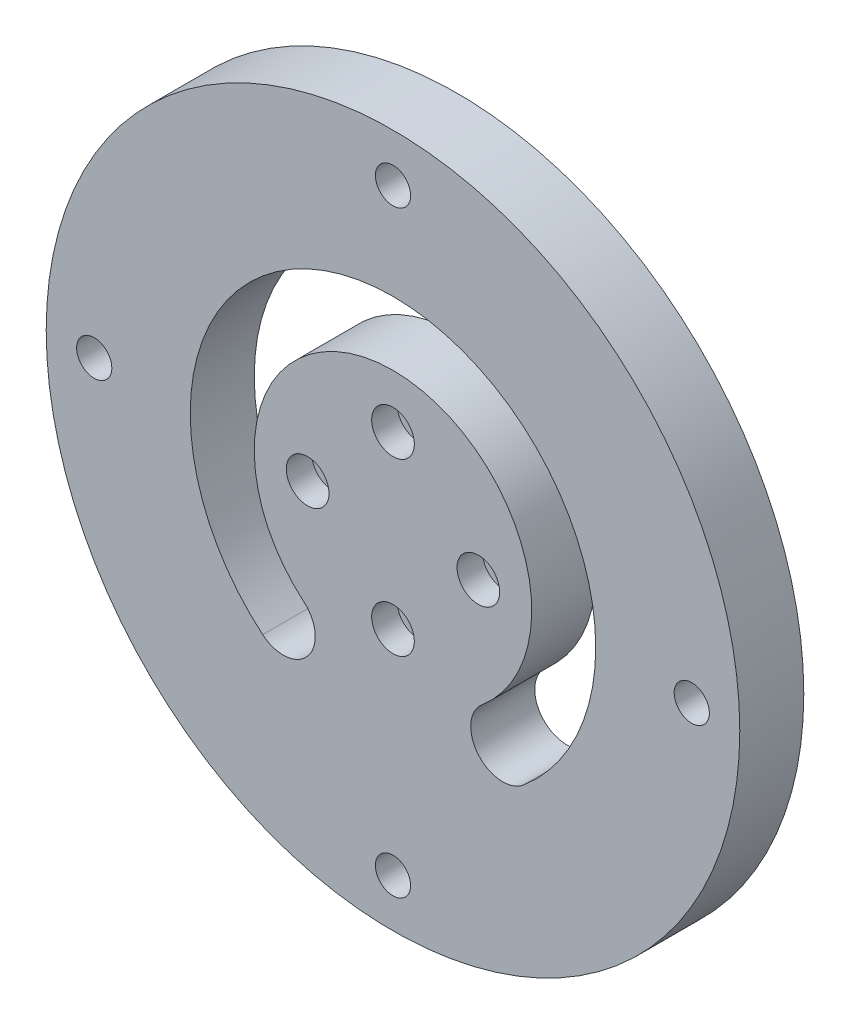
SolidWorks part; units mm, degrees
ref_plane "Front Plane" through (0, 0, 0) normal (0, 0, 1) x (1, 0, 0)
ref_plane "Top Plane" through (0, 0, 0) normal (0, 1, 0) x (1, 0, 0)
ref_plane "Right Plane" through (0, 0, 0) normal (1, 0, 0) x (0, 0, -1)
sketch "Sketch1" plane through (0, 0, 0) normal (0, 0, 1) x (1, 0, 0)
  circle A0 centre (0, 0) radius 32.5
  dimension "D1" = 65
extrude "Boss-Extrude1" add sketch "Sketch1" along normal blind 6
sketch "Sketch16" plane through (0, 0, 6) normal (0, 0, 1) x (1, 0, 0)
  line L0 (-8, 0) -> (8, 0) construction
  line L1 (0, 0) -> (0, -8) construction
  line L2 (0, 0) -> (0, 8) construction
  circle A0 centre (8, 0) radius 1.1
  circle A1 centre (-8, 0) radius 1.1
  circle A2 centre (0, -8) radius 1.1
  circle A3 centre (0, 8) radius 1.1
  point P6 (0, 0)
  dimension "D1" = 2.2
  dimension "D2" = 8
  dimension "D3" = 16
  dimension "D4" = 8
extrude "Cut-Extrude8" cut sketch "Sketch16" against normal through all
sketch "Sketch17" plane through (0, 0, 6) normal (0, 0, 1) x (1, 0, 0)
  circle A0 centre (8, 0) radius 2
  circle A1 centre (-8, 0) radius 2
  circle A2 centre (0, -8) radius 2
  circle A3 centre (0, 8) radius 2
  dimension "D1" = 4
extrude "Cut-Extrude9" cut sketch "Sketch17" against normal blind 2.4
sketch "Sketch12" plane through (0, 0, 6) normal (0, 0, 1) x (1, 0, 0)
  line L0 (0, 0) -> (0, 28) construction
  circle A4 centre (0, 28) radius 1.65
  circle A5 centre (28, 0) radius 1.65
  circle A6 centre (0, -28) radius 1.65
  circle A7 centre (-28, 0) radius 1.65
  point P14 (0, 0)
  dimension "D3" = 4
  dimension "D1" = 3.3
  dimension "D2" = 28
extrude "Cut-Extrude10" cut sketch "Sketch12" against normal through all
sketch "Sketch18" plane through (0, 0, 0) normal (0, 0, -1) x (-1, 0, 0)
  line L1 (1.6166, 30.8) -> (-1.6166, 30.8)
  line L2 (-1.6166, 30.8) -> (-3.2332, 28)
  line L3 (-3.2332, 28) -> (-1.6166, 25.2)
  line L4 (-1.6166, 25.2) -> (1.6166, 25.2)
  line L5 (1.6166, 25.2) -> (3.2332, 28)
  line L6 (3.2332, 28) -> (1.6166, 30.8)
  line L7 (29.6166, 2.8) -> (26.3834, 2.8)
  line L8 (26.3834, 2.8) -> (24.7668, 0)
  line L9 (24.7668, 0) -> (26.3834, -2.8)
  line L10 (26.3834, -2.8) -> (29.6166, -2.8)
  line L11 (29.6166, -2.8) -> (31.2332, 0)
  line L12 (31.2332, 0) -> (29.6166, 2.8)
  line L13 (1.6166, -25.2) -> (-1.6166, -25.2)
  line L14 (-1.6166, -25.2) -> (-3.2332, -28)
  line L15 (-3.2332, -28) -> (-1.6166, -30.8)
  line L16 (-1.6166, -30.8) -> (1.6166, -30.8)
  line L17 (1.6166, -30.8) -> (3.2332, -28)
  line L18 (3.2332, -28) -> (1.6166, -25.2)
  line L19 (-26.3834, 2.8) -> (-29.6166, 2.8)
  line L20 (-29.6166, 2.8) -> (-31.2332, 0)
  line L21 (-31.2332, 0) -> (-29.6166, -2.8)
  line L22 (-29.6166, -2.8) -> (-26.3834, -2.8)
  line L23 (-26.3834, -2.8) -> (-24.7668, 0)
  line L24 (-24.7668, 0) -> (-26.3834, 2.8)
  circle A0 centre (0, 28) radius 2.8 construction
  circle A1 centre (28, 0) radius 2.8 construction
  circle A2 centre (0, -28) radius 2.8 construction
  circle A3 centre (-28, 0) radius 2.8 construction
  dimension "D1" = 5.6
extrude "Cut-Extrude11" cut sketch "Sketch18" against normal blind 3
sketch "Sketch19" plane through (0, 0, 6) normal (0, 0, 1) x (1, 0, 0)
  line L0 (0, 0) -> (0, -19.652) construction
  line L1 (0, 0) -> (12.213, -14.5548) construction
  line L2 (0, 0) -> (-12.213, -14.5548) construction
  arc A0 (12.213, -14.5548) -> (-12.213, -14.5548) centre (0, 0) ccw
  arc A1 (8.3562, -9.9586) -> (-8.3562, -9.9586) centre (0, 0) ccw
  arc A2 (-12.213, -14.5548) -> (-8.3562, -9.9586) centre (-10.2846, -12.2567) ccw
  arc A3 (8.3562, -9.9586) -> (12.213, -14.5548) centre (10.2846, -12.2567) ccw
  dimension "D1" = 6
  dimension "D3" = 13
  dimension "D2" = 40
extrude "Cut-Extrude12" cut sketch "Sketch19" against normal through all
ref_point "Point1"
ref_axis "Axis1" through (0, 0, 6) along (0, 0, -1)
ref_axis "Axis2" through (8, 0, 0) along (0, 0, 1)
ref_axis "Axis3" through (0, 8, 0) along (0, 0, 1)
ref_plane "Plane1" through (0, 0, 0) normal (0, -1, 0) x (-1, 0, 0)
ref_plane "Plane2" through (0, 0, 0) normal (1, 0, 0) x (0, 0, -1)
ref_plane "Plane3" through (0, 0, 0) normal (0, 0, -1) x (-1, 0, 0)
ref_axis "Axis4" through (-14.813, 0, 0) along (1, 0, 0)
ref_axis "Axis5" through (0, -0.4, 0) along (0, 1, 0)
